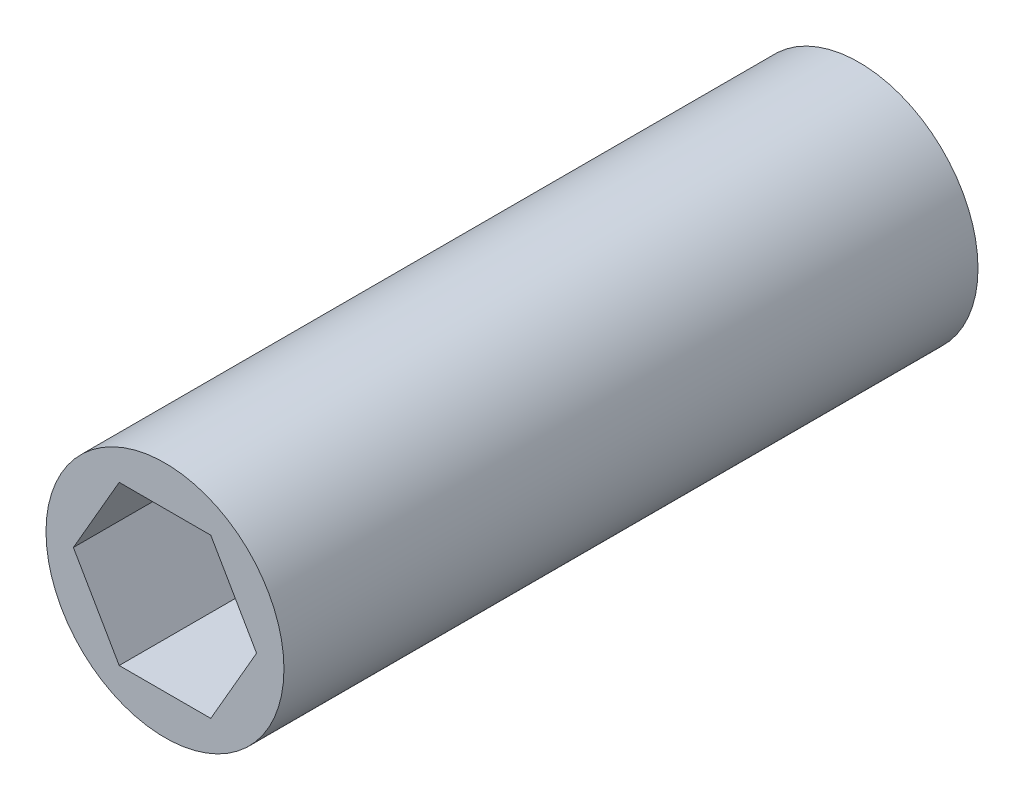
SolidWorks part; units mm, degrees
ref_plane "Front Plane" through (0, 0, 0) normal (0, 0, 1) x (1, 0, 0)
ref_plane "Top Plane" through (0, 0, 0) normal (0, 1, 0) x (1, 0, 0)
ref_plane "Right Plane" through (0, 0, 0) normal (1, 0, 0) x (0, 0, -1)
sketch "Sketch1" plane through (0, 0, 0) normal (0, 0, 1) x (1, 0, 0)
  line L1 (7.3323, 0) -> (3.6662, 6.35)
  line L2 (3.6662, 6.35) -> (-3.6662, 6.35)
  line L3 (-3.6662, 6.35) -> (-7.3323, 0)
  line L4 (-7.3323, 0) -> (-3.6662, -6.35)
  line L5 (-3.6662, -6.35) -> (3.6662, -6.35)
  line L6 (3.6662, -6.35) -> (7.3323, 0)
  circle A0 centre (0, 0) radius 6.35 construction
  circle A1 centre (0, 0) radius 9.525
  dimension "D2" = 19.05
  dimension "D1" = 12.7
extrude "Boss-Extrude1" add sketch "Sketch1" along normal mid plane 55.5625
